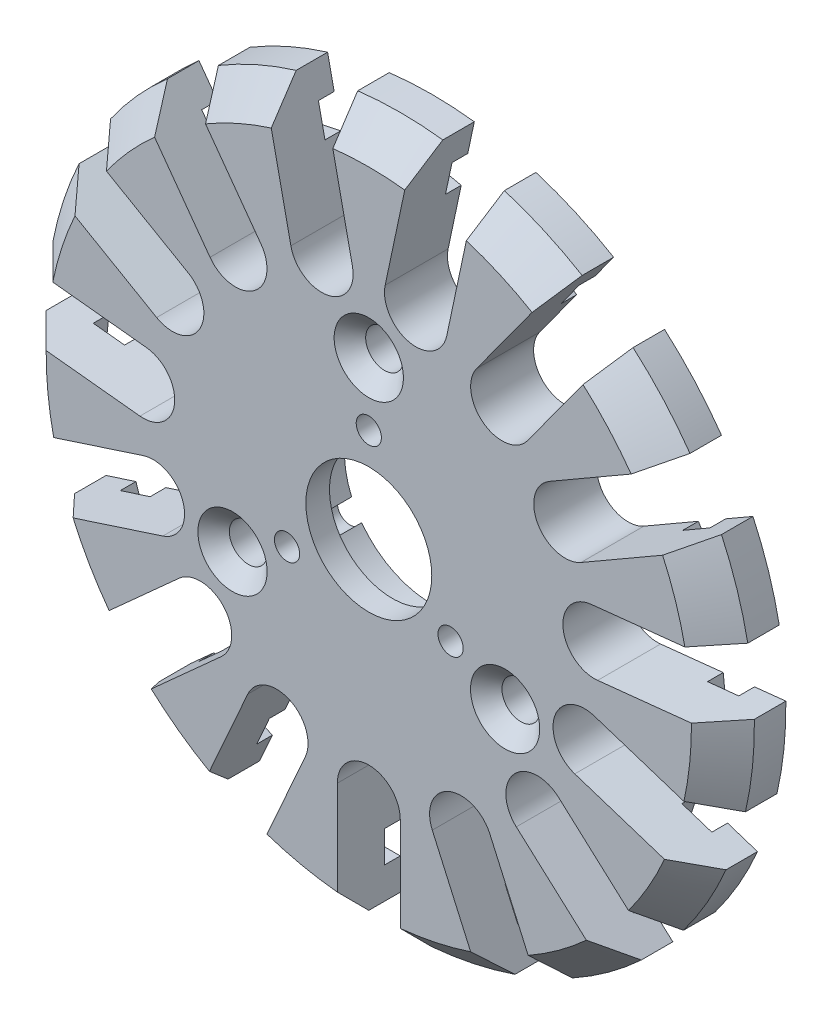
SolidWorks part; units mm, degrees
material "Liga 1060"
ref_plane "Plano frontal" through (0, 0, 0) normal (0, 0, 1) x (1, 0, 0)
ref_plane "Plano superior" through (0, 0, 0) normal (0, 1, 0) x (1, 0, 0)
ref_plane "Plano direito" through (0, 0, 0) normal (1, 0, 0) x (0, 0, -1)
sketch "Esboço1" plane through (0, 0, 0) normal (0, 0, 1) x (1, 0, 0)
  circle A0 centre (0, 0) radius 22.5
  dimension "D1" = 45
extrude "Ressalto-extrusão1" add sketch "Esboço1" along normal blind 4
chamfer "Chanfro1" distance 2 angle 45 1 edges at (22.5, 0, 4)
sketch "Esboço4" plane through (0, 0, 0) normal (0, 0, -1) x (-1, 0, 0)
  circle A0 centre (0, 0) radius 5.55
  dimension "D1" = 11.1
extrude "Corte-extrusão2" cut sketch "Esboço4" against normal blind 2.5 contours A0
sketch "Esboço5" plane through (0, 0, 2.5) normal (0, 0, -1) x (-1, 0, 0)
  circle A0 centre (0, 0) radius 4
  dimension "D1" = 8
extrude "Corte-extrusão3" cut sketch "Esboço5" against normal blind 2
sketch "Esboço6" plane through (0, 0, 0) normal (0, 0, -1) x (-1, 0, 0)
  line L0 (0, 0) -> (0, -22.5) construction
  line L1 (2, -22.4109) -> (2, -14.4109)
  line L2 (-2, -14.4109) -> (-2, -22.4109)
  circle A0 centre (0, 0) radius 22.5 construction
  arc A1 (-2, -22.4109) -> (2, -22.4109) centre (0, 0) ccw
  arc A2 (2, -14.4109) -> (-2, -14.4109) centre (0, -14.4109) ccw
  dimension "D1" = 4
  dimension "D2" = 8
extrude "Corte-extrusão4" cut sketch "Esboço6" against normal blind 4
pattern_circular "PadrãoCircular1" count 15 over 360 about axis through (0, 0, 2.5) along (0, 0, -1) of "Corte-extrusão4"
sketch "Esboço8" plane through (0, 0, 0) normal (0, 0, -1) x (-1, 0, 0)
  circle A0 centre (0, 0) radius 20.5
  circle A1 centre (0, 0) radius 18.5
  dimension "D1" = 41
  dimension "D2" = 37
sketch "Esboço9" plane through (0, 0, 4) normal (0, 0, 1) x (1, 0, 0)
  circle A0 centre (0, 0) radius 6
  circle A1 centre (0, 0) radius 4
  circle A2 centre (0, 0) radius 10
  point P4 (0, 6)
  point P6 (0, 10)
  dimension "D1" = 8
  dimension "D2" = 12
  dimension "D3" = 20
hole_wizard "Broca de rosquear para tarraxa de M21" positions "3DSketch1" profile "Esboço10" hole size "M2" standard "ISO" end condition through all
sketch3d "3DSketch1"
  point P0 (0, 6, 4)
sketch "Esboço10" plane through (0, 6, 4) normal (1, 0, 0) x (0, -1, 0)
  line L0 (0, 0) -> (0, 4)
  line L1 (0, 4) -> (0.8, 4)
  line L2 (0.8, 4) -> (0.8, 0)
  line L5 (0.8, 0) -> (0, 0)
  line L11 (0, -6.35) -> (0, 107.95) construction
  dimension "Thru Hole Dia." = 1.6
  dimension "Thru Hole Depth" = 4
hole_wizard "Escareado para parafuso com cabeça escareada chata de M21" positions "3DSketch2" profile "Esboço14" countersink size "M2" standard "ISO" end condition through all
sketch3d "3DSketch2"
  point P0 (0, 10, 4)
sketch "Esboço14" plane through (0, 10, 4) normal (1, 0, 0) x (0, -1, 0)
  line L0 (0, 0) -> (0, 4)
  line L1 (0, 4) -> (1.2, 4)
  line L2 (1.2, 4) -> (1.2, 1)
  line L3 (1.2, 1) -> (2.2, 0)
  line L5 (2.2, 0) -> (0, 0)
  line L6 (-1.2, 1) -> (-2.2, 0) construction
  line L11 (0, -6.35) -> (0, 107.95) construction
  dimension "Thru Hole Dia." = 2.4
  dimension "Thru Hole Depth" = 4
  dimension "Near C'Sink Dia." = 4.4
  dimension "Near C'Sink Angle" = 90
pattern_circular "PadrãoCircular2" count 3 over 360 about axis through (0, 0, 2.5) along (0, 0, -1) of "Broca de rosquear para tarraxa de M21" reverse direction yes
sketch "Esboço12" plane through (0, 0, 0) normal (0, 0, -1) x (-1, 0, 0)
  line L2 (3.5, -20.4109) -> (-3.5, -20.4109)
  line L3 (-3.5, -20.4109) -> (-3.5, -18.4109)
  line L4 (-3.5, -18.4109) -> (3.5, -18.4109)
  line L5 (3.5, -18.4109) -> (3.5, -20.4109)
  line L6 (0, 0) -> (0, -22.5) construction
  arc A0 (-7.2883, -21.2869) -> (-2, -22.4109) centre (0, 0) ccw construction
  point P0 (0, -18.4109)
  dimension "D1" = 2
  dimension "D2" = 7
  dimension "D3" = 2
extrude "Corte-extrusão5" cut sketch "Esboço12" against normal blind 1
pattern_circular "PadrãoCircular3" count 15 over 360 about axis through (0, 0, 2.5) along (0, 0, -1) of "Corte-extrusão5"
pattern_circular "PadrãoCircular4" count 3 over 360 about axis through (0, 0, 4) along (0, 0, 1) of "Escareado para parafuso com cabeça escareada chata de M21"
